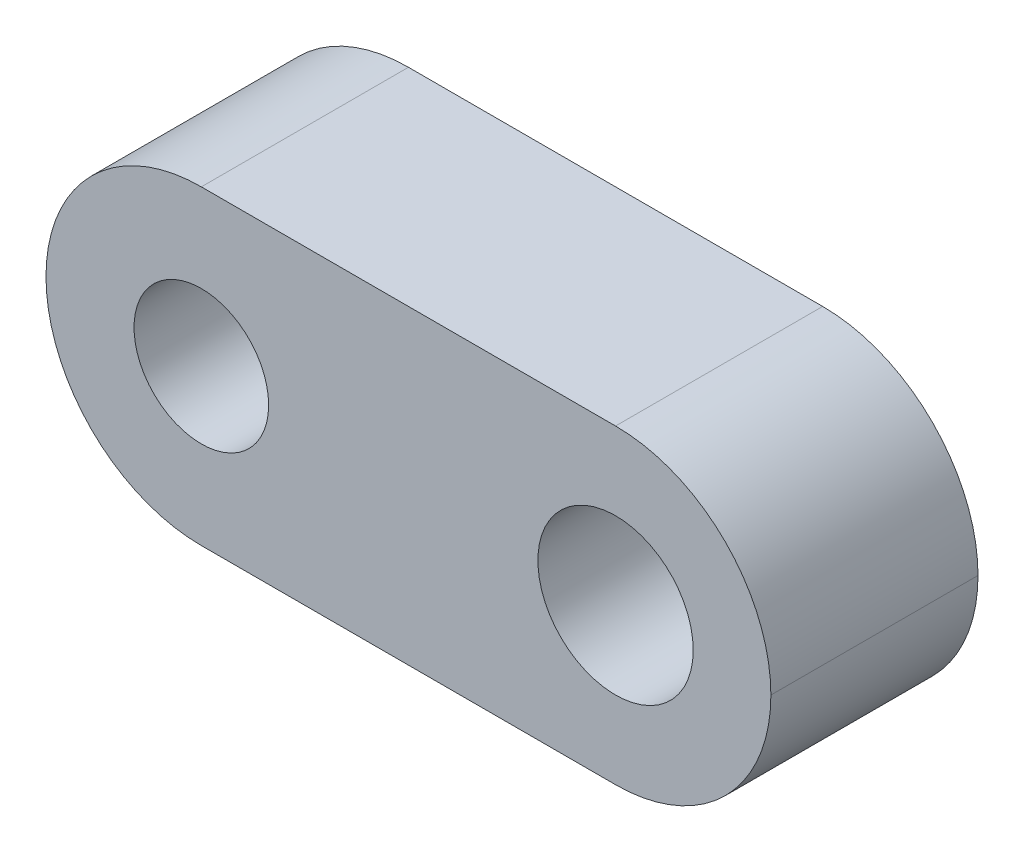
SolidWorks part; units mm, degrees
ref_plane "Front" through (0, 0, 0) normal (0, 0, 1) x (1, 0, 0)
ref_plane "Top" through (0, 0, 0) normal (0, 1, 0) x (1, 0, 0)
ref_plane "Right" through (0, 0, 0) normal (1, 0, 0) x (0, 0, -1)
sketch "Sketch1" plane through (0, 0, 0) normal (0, 0, 1) x (1, 0, 0)
  line L1 (0, 0) -> (14, 0)
  line L2 (0, 0) -> (0, -6)
  line L3 (0, -6) -> (14, -6)
  line L4 (14, 0) -> (14, -6)
  dimension "D1" = 6
  dimension "D2" = 14
extrude "Boss-Extrude1" add sketch "Sketch1" along normal blind 4
sketch "Sketch2" plane through (0, 0, 4) normal (0, 0, 1) x (1, 0, 0)
  line L0 (0, 0) -> (0, -6) construction
  line L1 (14, -6) -> (14, 0) construction
  circle A0 centre (3, -3) radius 1.3
  circle A1 centre (11, -3) radius 1.5
  dimension "D1" = 2.6
  dimension "D3" = 3
  dimension "D2" = 3
  dimension "D4" = 3
extrude "Cut-Extrude1" cut sketch "Sketch2" against normal through all and the other way through all
fillet "Fillet1" radius 3 4 edges at (14, -6, 2) (14, 0, 2) (0, -6, 2) (0, 0, 2)
equation "\"滑动-垂直孔\" = 0.6"
equation "\"滑动-水平孔\"= 0.3"
equation "\"松动-垂直孔\" = 0.3"
equation "\"松动-水平孔\"= 0.1"
equation "\"正常-垂直孔\" = 0.15"
equation "\"正常-水平孔\"= 0"
equation "\"紧缩-垂直孔\"= 0"
equation "\"紧缩-水平孔\"= - 0.1"
equation "\"D1@Sketch2\"=\"滑动-垂直孔\"+2"
equation "\"D3@Sketch2\"=\"紧缩-垂直孔\"+3"
